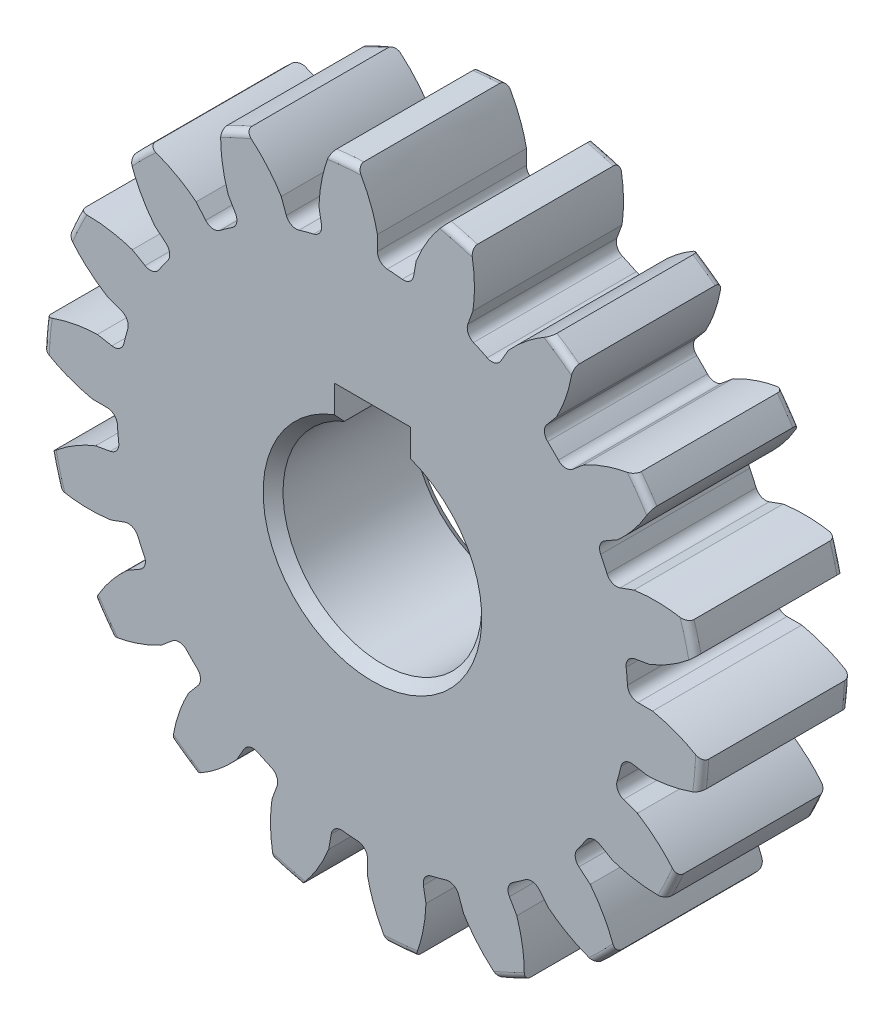
SolidWorks part; units mm, degrees
ref_plane "Front" through (0, 0, 0) normal (0, 0, 1) x (1, 0, 0)
ref_plane "Top" through (0, 0, 0) normal (0, 1, 0) x (1, 0, 0)
ref_plane "Right" through (0, 0, 0) normal (1, 0, 0) x (0, 0, -1)
sketch "Sketch1" plane through (0, 0, 0) normal (0, 0, 1) x (1, 0, 0)
  line L0 (-228.6, 0) -> (228.6, 0) construction
  circle A0 centre (0, 0) radius 10.541
  circle A1 centre (0, 0) radius 9.525 construction
  circle A3 centre (0, 0) radius 8.1598 construction
  dimension "D3" = 1.016
  dimension "D1" = 2.3813
extrude "Boss-Extrude1" add sketch "Sketch1" against normal blind 4.7625
sketch "Sketch2" plane through (0, 0, 0) normal (1, 0, 0) x (0, 0, -1)
  line L0 (4.7625, 0) -> (11.0998, 0)
  line L1 (4.7625, 0) -> (4.7625, 6.35)
  line L2 (4.7625, 6.35) -> (11.0998, 6.35)
  line L3 (11.0998, 6.35) -> (11.0998, 0)
  point P5 (11.0998, -6.35)
  point P6 (0, -10.541)
  point P7 (4.7625, -10.541)
  point P9 (0, 10.541)
revolve "Revolve1" add sketch "Sketch2" angle 360 mid plane about L0
fillet "Fillet2" radius 0.2108 3 edges at (10.541, 0, -4.7625) (10.541, 0, 0) (6.35, 0, -4.7625)
sketch "Sketch3" plane through (0, 0, 0) normal (0, 0, 1) x (1, 0, 0)
  line L0 (0, 0) -> (0, 10.541) construction
  line L1 (-3.0613, 8.4108) -> (0, 9.525)
  line L2 (-9.5921, 9.525) -> (9.5921, 9.525) construction
  line L3 (-9.0136, 6.2443) -> (9.0136, 12.8057) construction
  line L4 (-3.0613, 8.4108) -> (0, 0) construction
  line L5 (-7.3721, 5.0759) -> (0, 0) construction
  line L6 (-7.3721, 5.0759) -> (-2.3984, 12.2997) construction
  line L7 (-2.1265, 8.6943) -> (0, 0) construction
  line L8 (-2.1265, 8.6943) -> (0.0886, 9.2361) construction
  arc A0 (-3.0613, 8.4108) -> (-7.3721, 5.0759) centre (0, 0) ccw
  circle A1 centre (0, 0) radius 9.525 construction
  circle A2 centre (0, 0) radius 8.9506 construction
  arc A3 (-3.0613, 8.4108) -> (-2.1265, 8.6943) centre (0, 0) cw
  circle A4 centre (0, 0) radius 10.541 construction
  point P6 (0, 9.525)
  dimension "D1" = 3.2577
  dimension "Pressure Angle" = 20
  dimension "D2" = 5.5382
  dimension "D3" = 8.7705
  dimension "D4" = 0.9773
  dimension "D5" = 2.2804
sketch "Sketch4" plane through (0, 0, 0) normal (0, 0, 1) x (1, 0, 0)
  line L0 (0, 0) -> (0.827, 9.4526) construction
  line L1 (0.1576, 8.9492) -> (0.1576, 8.1582)
  line L2 (0, 9.525) -> (1.654, 9.3803) construction
  line L3 (1.3988, 8.8406) -> (1.2615, 8.0616)
  line L4 (0.1576, 8.1582) -> (0, 0) construction
  line L5 (0, 0) -> (0, 10.541) construction
  line L6 (-7.3721, 5.0759) -> (-2.3984, 12.2997) construction
  line L7 (-7.3721, 5.0759) -> (-2.3984, 12.2997) construction
  arc A0 (1.2615, 8.0616) -> (0.1576, 8.1582) centre (0, 0) ccw
  arc A1 (0, 9.525) -> (1.654, 9.3803) centre (0, 0) cw construction
  circle A2 centre (0, 0) radius 9.525 construction
  circle A3 centre (0, 0) radius 8.9506 construction
  circle A4 centre (0, 0) radius 8.1598 construction
  arc A5 (4.4978, 11.6964) -> (-2.3984, 12.2997) centre (0, 0) ccw
  spline S0 degree 2 poles (-2.3984, 12.2997) (-0.2792, 11.04) (0.1576, 8.9492) knots 0 0 0 1 1 1
  spline S1 degree 2 poles (4.4978, 11.6964) (2.1921, 10.8237) (1.3988, 8.8406) knots 0 0 0 1 1 1
  dimension "D1" = 1.6624
extrude "Cut-Extrude1" cut sketch "Sketch4" against normal through all
fillet "Fillet1" radius 0.3325 2 edges at (1.2615, 8.0616, -2.3813) (0.1576, 8.1582, -2.3813)
pattern_circular "CirPattern1" count 18 over 360 about axis through (0, 0, -4.7625) along (0, 0, 1) of "Cut-Extrude1", "Fillet1"
sketch "Sketch5" plane through (0, 0, 0) normal (0, 0, 1) x (1, 0, 0)
  line L0 (0, 4.3663) -> (0, 0) construction
  line L1 (-1.1906, 2.9433) -> (1.1906, 2.9433) construction
  line L2 (-1.1906, 2.9433) -> (-1.1906, 4.3663) construction
  line L3 (-1.1906, 4.3663) -> (1.1906, 4.3663) construction
  line L4 (1.1906, 2.9433) -> (1.1906, 4.3663) construction
  line L5 (-1.1906, 2.9433) -> (1.1906, 4.3663) construction
  line L6 (-1.1906, 4.3663) -> (1.1906, 2.9433) construction
  circle A0 centre (0, 0) radius 3.175
  point P3 (0, 3.6548)
  point P8 (0, 3.175)
  point P9 (0, -3.175)
  dimension "Bore Min" = 6.35
  dimension "Keyway Wd" = 2.3813
  dimension "Keyway Dpt." = 1.1913
extrude "Cut-Extrude2" cut sketch "Sketch5" against normal through all
sketch "Pitch Dia" plane through (0, 0, 0) normal (0, 0, 1) x (1, 0, 0)
  circle A0 centre (0, 0) radius 9.525 construction
  circle A1 centre (0, 0) radius 9.525 construction
sketch "Sketch6" plane through (0, 0, -4.7625) normal (0, 0, -1) x (-1, 0, 0)
  circle A0 centre (0, 0) radius 9.525
  dimension "D1" = 19.05
extrude "Cut-Extrude3" cut sketch "Sketch6" along normal through all
chamfer "Chamfer1" distance 0.3175 angle 45 2 edges at (3.175, 0, 0) (-3.175, 0, -4.7625)
sketch "Sketch7" plane through (0, 0, -4.7625) normal (0, 0, -1) x (-1, 0, 0)
  line L0 (0, 10.8347) -> (0, -11.529) construction
  line L1 (-1.216, 1.7169) -> (1.216, 1.7169)
  line L2 (-1.216, 1.7169) -> (-1.216, 4.1489)
  line L3 (-1.216, 4.1489) -> (1.216, 4.1489)
  line L4 (1.216, 1.7169) -> (1.216, 4.1489)
  line L5 (-14.1417, 2.9329) -> (12.5826, 2.9329) construction
  circle A2 centre (0, 0) radius 3.175 construction
  point P7 (1.216, 2.9329)
  point P8 (0, 0)
  point P11 (-1.216, 2.9329)
  dimension "D1" = 2.432
  dimension "D2" = 2.432
extrude "Cut-Extrude4" cut sketch "Sketch7" against normal through all both and the other way through all
equation "\"D1@Boss-Extrude1\" = \"Face Wd@Sketch2\""
equation "\"D1@Sketch4\" = 1.5708/(\"Number of Teeth@Sketch1\"/\"Ptich Dia@Sketch1\")"
equation "\"D1@Chamfer1\" = \"B Hub Dia@Sketch2\"*.025"
equation "\"D1@CirPattern1\" = \"Number of Teeth@Sketch1\""
equation "\"D1@Fillet1\" = \"D1@Sketch4\"*.2"
equation "\"D1@Fillet2\" = \"OD@Sketch1\"*.01"
equation "\"D1@Sketch1\" = 2.250/(\"Number of Teeth@Sketch1\"/\"Ptich Dia@Sketch1\")"
